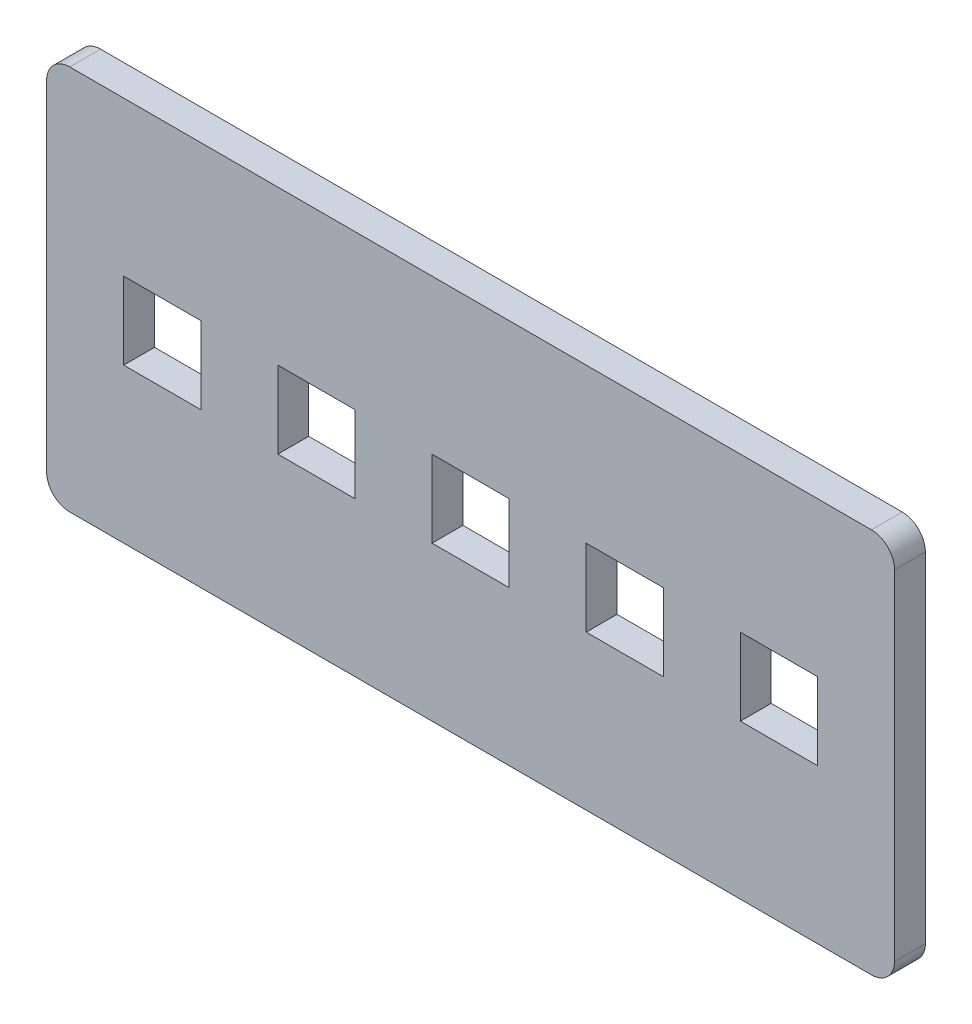
SolidWorks part; units mm, degrees
ref_plane "Plan de face" through (0, 0, 0) normal (0, 0, 1) x (1, 0, 0)
ref_plane "Plan de dessus" through (0, 0, 0) normal (0, 1, 0) x (1, 0, 0)
ref_plane "Plan de droite" through (0, 0, 0) normal (1, 0, 0) x (0, 0, -1)
sketch "Esquisse1" plane through (0, 0, 0) normal (0, 0, 1) x (1, 0, 0)
  line L0 (-42.5339, 0) -> (40.0525, 0) construction
  line L1 (55, -25) -> (-55, -25)
  line L2 (55, -25) -> (55, 25)
  line L3 (55, 25) -> (-55, 25)
  line L4 (-55, -25) -> (-55, 25)
  line L5 (55, -25) -> (-55, 25) construction
  line L6 (55, 25) -> (-55, -25) construction
  line L7 (-25, 5) -> (-15, 5)
  line L8 (-45, 5) -> (-35, 5)
  line L9 (-45, 5) -> (-45, -5)
  line L10 (-45, -5) -> (-35, -5)
  line L11 (-35, 5) -> (-35, -5)
  line L12 (-45, 5) -> (-35, -5) construction
  line L13 (-45, -5) -> (-35, 5) construction
  line L14 (-25, 5) -> (-25, -5)
  line L15 (-25, -5) -> (-15, -5)
  line L16 (-15, 5) -> (-15, -5)
  line L17 (-25, 5) -> (-15, -5) construction
  line L18 (-25, -5) -> (-15, 5) construction
  line L19 (-5, 5) -> (5, 5)
  line L20 (-5, 5) -> (-5, -5)
  line L21 (-5, -5) -> (5, -5)
  line L22 (5, 5) -> (5, -5)
  line L23 (-5, 5) -> (5, -5) construction
  line L24 (-5, -5) -> (5, 5) construction
  line L25 (15, 5) -> (25, 5)
  line L26 (15, 5) -> (15, -5)
  line L27 (15, -5) -> (25, -5)
  line L28 (25, 5) -> (25, -5)
  line L29 (15, 5) -> (25, -5) construction
  line L30 (15, -5) -> (25, 5) construction
  line L31 (35, 5) -> (45, 5)
  line L32 (35, 5) -> (35, -5)
  line L33 (35, -5) -> (45, -5)
  line L34 (45, 5) -> (45, -5)
  line L35 (35, 5) -> (45, -5) construction
  line L36 (35, -5) -> (45, 5) construction
  point P0 (0, 0)
  point P8 (-40, 0)
  point P14 (-20, 0)
  point P19 (0, 0)
  point P24 (20, 0)
  point P29 (40, 0)
  dimension "D1" = 110
  dimension "D2" = 50
  dimension "D3" = 10
  dimension "D4" = 10
  dimension "D5" = 10
  dimension "D6" = 5
extrude "Boss.-Extru.1" add sketch "Esquisse1" along normal blind 4
fillet "Congé1" radius 3 4 edges at (55, 25, 2) (55, -25, 2) (-55, -25, 2) (-55, 25, 2)
ref_plane "Plan1" through (0, 0, 0) normal (0, -1, 0) x (-1, 0, 0)
ref_plane "Plan2" through (-40, 0, 0) normal (-1, 0, 0) x (0, 0, 1)
ref_plane "Plan3" through (-20, 0, 0) normal (-1, 0, 0) x (0, 0, 1)
ref_plane "Plan4" through (0, 0, 0) normal (1, 0, 0) x (0, 0, -1)
ref_plane "Plan5" through (20, 0, 0) normal (-1, 0, 0) x (0, 0, 1)
ref_plane "Plan6" through (40, 0, 0) normal (1, 0, 0) x (0, 0, -1)
ref_axis "Axe1" through (-40, 0, 9.7524) along (0, 0, -1)
